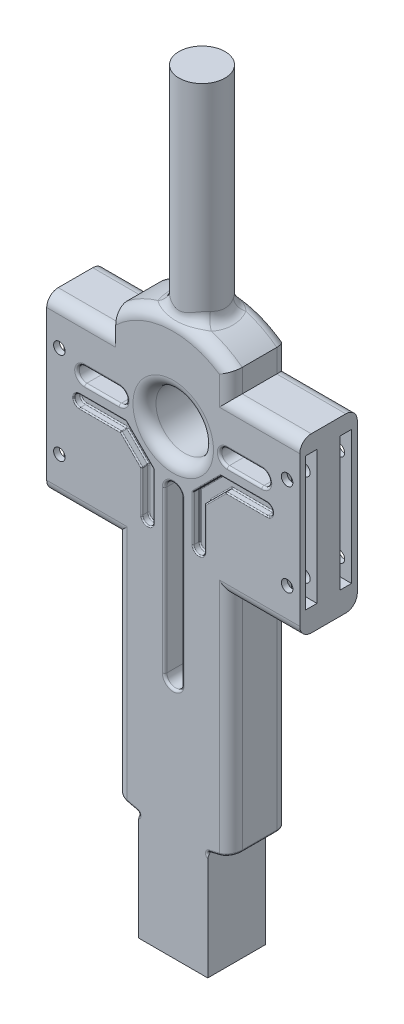
SolidWorks part; units mm, degrees
ref_plane "Спереди" through (0, 0, 0) normal (0, 0, 1) x (1, 0, 0)
ref_plane "Сверху" through (0, 0, 0) normal (0, 1, 0) x (1, 0, 0)
ref_plane "Справа" through (0, 0, 0) normal (1, 0, 0) x (0, 0, -1)
sketch "Эскиз1" plane through (0, 0, 0) normal (0, 0, 1) x (1, 0, 0)
  line L0 (-25, 0) -> (25, 0) construction
  line L5 (25, 0) -> (25, 97.3699)
  line L6 (25, 182.3699) -> (-25, 182.3699) construction
  line L7 (0, 0) -> (0, 137.8365) construction
  line L8 (-25, 0) -> (-25, 97.3699)
  line L9 (25, 172.3699) -> (55, 172.3699)
  line L10 (55, 172.3699) -> (55, 97.3699)
  line L11 (55, 97.3699) -> (25, 97.3699)
  line L12 (-55, 97.3699) -> (-25, 97.3699)
  line L13 (-55, 172.3699) -> (-55, 97.3699)
  line L14 (-25, 172.3699) -> (-55, 172.3699)
  line L15 (-25, 172.3699) -> (-25, 182.3699)
  line L16 (25, 172.3699) -> (25, 182.3699)
  arc A1 (25, 182.3699) -> (-25, 182.3699) centre (0, 150) ccw
  circle A2 centre (0, 150) radius 12.5
  arc A3 (-25, 0) -> (25, 0) centre (0, 74.94) ccw
  point P0 (0, 0)
  point P9 (0, 182.3699)
  dimension "D1" = 50
  dimension "D2" = 40.9
  dimension "D3" = 25
  dimension "D5" = 79
  dimension "D4" = 150
  dimension "D6" = 30
  dimension "D7" = 75
  dimension "D8" = 10
extrude "Бобышка-Вытянуть1" add sketch "Эскиз1" along normal blind 25
fillet "Скругление1" radius 5 2 edges at (12.5, 150, 0) (12.5, 150, 25)
fillet "Скругление2" radius 5 16 edges at (-25, 48.6849, 25) (-25, 48.6849, 0) (-40, 97.3699, 0) (-40, 97.3699, 25) (25, 48.6849, 0) (40, 97.3699, 0) (25, 48.6849, 25) (40, 97.3699, 25) (-40, 172.3699, 25) (-40, 172.3699, 0) (0, 190.9, 0) (25, 177.3699, 0) (40, 172.3699, 0) (40, 172.3699, 25) (25, 177.3699, 25) (0, 190.9, 25)
ref_plane "Плоскость1" through (0, 180, 0) normal (0, 1, 0) x (1, 0, 0)
sketch "Эскиз2" plane through (0, 180, 0) normal (0, 1, 0) x (1, 0, 0)
  line L0 (0, 0) -> (0, -25) construction
  line L1 (-25, -25) -> (20, -25) construction
  circle A0 centre (0, -12.5) radius 10
  dimension "D1" = 20
extrude "Бобышка-Вытянуть2" add sketch "Эскиз2" along normal blind 100
fillet "Скругление3" radius 5 4 edges at (-1.9459, 190.288, 2.6911) (-9.7288, 189.7261, 10.187) (9.9937, 189.6603, 12.8546) (1.9198, 190.2866, 22.314)
sketch "Эскиз3" plane through (0, 0, 0) normal (0, 0, 1) x (1, 0, 0)
  line L0 (0, 222.8155) -> (0, 47.6658) construction
  line L1 (23.5, 150) -> (38.5, 150) construction
  line L2 (78.8977, 150) -> (-76.0717, 150) construction
  line L3 (23.5, 153.3365) -> (38.5, 153.3365)
  line L4 (23.5, 146.6635) -> (38.5, 146.6635)
  line L5 (50, 180) -> (-50, 180) construction
  line L6 (37.4973, 140.3809) -> (21.8861, 140.3809) construction
  line L7 (21.8861, 140.3809) -> (7.5052, 126) construction
  line L8 (7.5052, 126) -> (7.5052, 110.5792) construction
  line L9 (37.4973, 136.3809) -> (23.5429, 136.3809) construction
  line L10 (23.5429, 136.3809) -> (11.5052, 124.3431) construction
  line L11 (11.5052, 124.3431) -> (11.5052, 110.5792) construction
  line L13 (-23.5, 150) -> (-38.5, 150) construction
  line L14 (-23.5, 153.3365) -> (-38.5, 153.3365)
  line L15 (-23.5, 146.6635) -> (-38.5, 146.6635)
  line L16 (-23.5429, 136.3809) -> (-11.5052, 124.3431) construction
  line L17 (-37.4973, 136.3809) -> (-23.5429, 136.3809) construction
  line L18 (-37.4973, 140.3809) -> (-21.8861, 140.3809) construction
  line L19 (-21.8861, 140.3809) -> (-7.5052, 126) construction
  line L20 (-7.5052, 126) -> (-7.5052, 110.5792) construction
  line L21 (-11.5052, 124.3431) -> (-11.5052, 110.5792) construction
  line L22 (0, 125) -> (0, 55) construction
  line L23 (3.75, 125) -> (3.75, 55)
  line L24 (-3.75, 125) -> (-3.75, 55)
  arc A0 (23.5, 153.3365) -> (23.5, 146.6635) centre (23.5, 150) ccw
  arc A1 (38.5, 146.6635) -> (38.5, 153.3365) centre (38.5, 150) ccw
  arc A2 (7.5052, 110.5792) -> (11.5052, 110.5792) centre (9.5052, 110.5019) ccw construction
  arc A3 (37.4973, 136.3809) -> (37.4973, 140.3809) centre (37.4973, 138.3809) ccw construction
  arc A4 (-23.5, 153.3365) -> (-23.5, 146.6635) centre (-23.5, 150) cw
  arc A5 (-38.5, 146.6635) -> (-38.5, 153.3365) centre (-38.5, 150) cw
  arc A6 (-37.4973, 136.3809) -> (-37.4973, 140.3809) centre (-37.4973, 138.3809) cw construction
  arc A7 (-7.5052, 110.5792) -> (-11.5052, 110.5792) centre (-9.5052, 110.5019) cw construction
  arc A8 (3.75, 125) -> (-3.75, 125) centre (0, 125) ccw
  arc A9 (-3.75, 55) -> (3.75, 55) centre (0, 55) ccw
  point P5 (0, 90)
  point P8 (31, 150)
  point P27 (-31, 150)
  dimension "D6" = 4.003
  dimension "D1" = 15
  dimension "D2" = 6.673
  dimension "D3" = 31
  dimension "D4" = 30
  dimension "D5" = 4
  dimension "D7" = 24
  dimension "D8" = 19.2381
  dimension "D9" = 7.5052
  dimension "D10" = 135
  dimension "D11" = 15.4981
  dimension "D12" = 15.6112
  dimension "D13" = 70
  dimension "D14" = 90
  dimension "D15" = 7.5
extrude "Вырез-Вытянуть2" cut sketch "Эскиз3" against normal through all both and the other way through all
fillet "Скругление4" radius 1 24 edges at (-41.8365, 150, 0) (-31, 153.3365, 0) (-20.1635, 150, 0) (20.1635, 150, 0) (31, 153.3365, 0) (41.8365, 150, 0) (-3.75, 90, 0) (0, 128.75, 0) (3.75, 90, 0) (0, 128.75, 25) (3.75, 90, 25) (0, 51.25, 25) (-31, 153.3365, 25) (-20.1635, 150, 25) (31, 153.3365, 25) (41.8365, 150, 25) (31, 146.6635, 25) (-31, 146.6635, 0) (-31, 146.6635, 25) (31, 146.6635, 0) (0, 51.25, 0) (-3.75, 90, 25) (-41.8365, 150, 25) (20.1635, 150, 25)
sketch "Эскиз4" plane through (0, 0, 0) normal (0, 0, 1) x (1, 0, 0)
  line L0 (0, 180) -> (0, 62.1656) construction
  line L1 (50, 180) -> (-50, 180) construction
  line L2 (8.6711, 109.7427) -> (8.6711, 129.7427)
  line L3 (8.6711, 129.7427) -> (20.6919, 141.7635)
  line L4 (20.6919, 141.7635) -> (40.6919, 141.7635)
  line L5 (4.75, 125) -> (4.75, 55) construction
  line L6 (38.5, 145.6635) -> (23.5, 145.6635) construction
  line L7 (13.6711, 109.7427) -> (13.6711, 127.6716)
  line L8 (13.6711, 127.6716) -> (22.7629, 136.7635)
  line L9 (22.7629, 136.7635) -> (40.6919, 136.7635)
  line L10 (-8.6711, 129.7427) -> (-20.6919, 141.7635)
  line L11 (-8.6711, 109.7427) -> (-8.6711, 129.7427)
  line L12 (-13.6711, 109.7427) -> (-13.6711, 127.6716)
  line L13 (-13.6711, 127.6716) -> (-22.7629, 136.7635)
  line L14 (-22.7629, 136.7635) -> (-40.6919, 136.7635)
  line L15 (-20.6919, 141.7635) -> (-40.6919, 141.7635)
  arc A0 (8.6711, 109.7427) -> (13.6711, 109.7427) centre (11.1711, 109.7427) ccw
  arc A1 (40.6919, 136.7635) -> (40.6919, 141.7635) centre (40.6919, 139.2635) ccw
  arc A2 (-8.6711, 109.7427) -> (-13.6711, 109.7427) centre (-11.1711, 109.7427) cw
  arc A3 (-40.6919, 136.7635) -> (-40.6919, 141.7635) centre (-40.6919, 139.2635) cw
  dimension "D1" = 3.9211
  dimension "D2" = 3.9
  dimension "D3" = 135
  dimension "D4" = 17
  dimension "D5" = 5
  dimension "2" = 20
  dimension "D6" = 20
extrude "Вырез-Вытянуть3" cut sketch "Эскиз4" along normal blind 3
fillet "Скругление5" radius 0.5 12 edges at (-13.6711, 118.7071, 0) (-31.7274, 136.7635, 0) (-11.1711, 107.2427, 0) (-43.1919, 139.2635, 0) (-8.6711, 119.7427, 0) (-30.6919, 141.7635, 0) (-18.217, 132.2175, 0) (-14.6815, 135.7531, 0) (-22.7629, 136.7635, 1.5) (-13.6711, 127.6716, 1.5) (-8.6711, 129.7427, 1.5) (-20.6919, 141.7635, 1.5)
fillet "Скругление6" radius 0.5 12 edges at (13.6711, 118.7071, 0) (11.1711, 107.2427, 0) (8.6711, 119.7427, 0) (14.6815, 135.7531, 0) (31.7274, 136.7635, 0) (30.6919, 141.7635, 0) (18.217, 132.2175, 0) (43.1919, 139.2635, 0) (22.7629, 136.7635, 1.5) (13.6711, 127.6716, 1.5) (8.6711, 129.7427, 1.5) (20.6919, 141.7635, 1.5)
fillet "Скругление7" radius 0.5 24 edges at (-20.7076, 141.7254, 3) (-14.6815, 135.7531, 3) (-8.7091, 129.7269, 3) (-8.6711, 119.6391, 3) (-11.1711, 107.2427, 3) (-13.6711, 118.6036, 3) (-13.7091, 127.6558, 3) (-18.217, 132.2175, 3) (-22.7787, 136.7254, 3) (-31.831, 136.7635, 3) (-43.1919, 139.2635, 3) (20.7076, 141.7254, 3) (30.7954, 141.7635, 3) (43.1919, 139.2635, 3) (31.831, 136.7635, 3) (22.7787, 136.7254, 3) (18.217, 132.2175, 3) (13.7091, 127.6558, 3) (13.6711, 118.6036, 3) (11.1711, 107.2427, 3) (8.6711, 119.6391, 3) (8.7091, 129.7269, 3) (-30.7954, 141.7635, 3) (14.6815, 135.7531, 3)
sketch "Эскиз5" plane through (0, 0, 25) normal (0, 0, 1) x (1, 0, 0)
  line L0 (0, 180) -> (0, 39.8773) construction
  line L1 (50, 180) -> (-50, 180) construction
  line L2 (8.65, 109.7427) -> (8.65, 129.7427)
  line L3 (8.65, 129.7427) -> (20.6708, 141.7635)
  line L4 (20.6708, 141.7635) -> (40.6708, 141.7635)
  line L5 (13.65, 109.7427) -> (13.65, 127.6716)
  line L6 (4.75, 125) -> (4.75, 55) construction
  line L7 (38.5, 145.6635) -> (23.5, 145.6635) construction
  line L8 (13.65, 127.6716) -> (22.7419, 136.7635)
  line L9 (22.7419, 136.7635) -> (40.6708, 136.7635)
  line L10 (-13.65, 109.7427) -> (-13.65, 127.6716)
  line L11 (-8.65, 109.7427) -> (-8.65, 129.7427)
  line L12 (-13.65, 127.6716) -> (-22.7419, 136.7635)
  line L13 (-8.65, 129.7427) -> (-20.6708, 141.7635)
  line L14 (-20.6708, 141.7635) -> (-40.6708, 141.7635)
  line L15 (-22.7419, 136.7635) -> (-40.6708, 136.7635)
  arc A0 (8.65, 109.7427) -> (13.65, 109.7427) centre (11.15, 109.7427) ccw
  arc A1 (40.6708, 136.7635) -> (40.6708, 141.7635) centre (40.6708, 139.2635) ccw
  arc A2 (-8.65, 109.7427) -> (-13.65, 109.7427) centre (-11.15, 109.7427) cw
  arc A3 (-40.6708, 136.7635) -> (-40.6708, 141.7635) centre (-40.6708, 139.2635) cw
  dimension "D1" = 20
  dimension "D2" = 17
  dimension "D3" = 20
  dimension "D4" = 135
  dimension "D5" = 3.9
  dimension "D6" = 3.9
  dimension "D7" = 5
extrude "Вырез-Вытянуть4" cut sketch "Эскиз5" against normal blind 3
fillet "Скругление8" radius 0.5 40 edges at (-13.65, 118.7071, 25) (-31.7063, 136.7635, 25) (-30.6708, 141.7635, 22) (-8.65, 119.7427, 22) (-11.15, 107.2427, 25) (-43.1708, 139.2635, 25) (-43.1708, 139.2635, 22) (-11.15, 107.2427, 22) (-8.65, 119.7427, 25) (-30.6708, 141.7635, 25) (-31.7063, 136.7635, 22) (-13.65, 118.7071, 22) (31.7063, 136.7635, 25) (43.1708, 139.2635, 25) (8.65, 119.7427, 25) (11.15, 107.2427, 25) (30.6708, 141.7635, 22) (43.1708, 139.2635, 22) (13.65, 118.7071, 22) (11.15, 107.2427, 22) (-8.65, 129.7427, 23.5) (-14.6604, 135.7531, 22) (-20.6708, 141.7635, 23.5) (-14.6604, 135.7531, 25) (22.7419, 136.7635, 23.5) (13.65, 127.6716, 23.5) (20.6708, 141.7635, 23.5) (8.65, 129.7427, 23.5) (30.6708, 141.7635, 25) (14.6604, 135.7531, 25) (13.65, 118.7071, 25) (18.1959, 132.2175, 25) (31.7063, 136.7635, 22) (18.1959, 132.2175, 22) (8.65, 119.7427, 22) (14.6604, 135.7531, 22) (-18.1959, 132.2175, 25) (-18.1959, 132.2175, 22) (-22.7419, 136.7635, 23.5) (-13.65, 127.6716, 23.5)
sketch "Эскиз6" plane through (-55, 0, 0) normal (-1, 0, 0) x (0, 0, 1)
  line L0 (12.5, 182.3699) -> (12.5, 74.6453) construction
  line L1 (20, 182.3699) -> (5, 182.3699) construction
  line L2 (0, 134.8699) -> (25, 134.8699) construction
  line L3 (0, 167.3699) -> (0, 102.3699) construction
  line L4 (25, 167.3699) -> (25, 102.3699) construction
  line L5 (2.5, 163.8699) -> (2.5, 105.8699)
  line L6 (2.5, 105.8699) -> (7.5, 105.8699)
  line L7 (7.5, 105.8699) -> (7.5, 163.8699)
  line L8 (7.5, 163.8699) -> (2.5, 163.8699)
  line L9 (22.5, 105.8699) -> (17.5, 105.8699)
  line L10 (17.5, 105.8699) -> (17.5, 163.8699)
  line L11 (17.5, 163.8699) -> (22.5, 163.8699)
  line L12 (22.5, 163.8699) -> (22.5, 105.8699)
  dimension "D1" = 29
  dimension "D2" = 29
  dimension "D3" = 5
  dimension "D4" = 10
extrude "Вырез-Вытянуть5" cut sketch "Эскиз6" against normal blind 11
sketch "Эскиз7" plane through (55, 0, 0) normal (1, 0, 0) x (0, 0, -1)
  line L0 (-12.5, 182.3699) -> (-12.5, 90.6991) construction
  line L1 (-20, 182.3699) -> (-5, 182.3699) construction
  line L2 (-25, 136.2635) -> (0, 136.2635) construction
  line L3 (-22.5, 165.2635) -> (-22.5, 107.2635)
  line L4 (-22.5, 107.2635) -> (-17.5, 107.2635)
  line L5 (-17.5, 107.2635) -> (-17.5, 165.2635)
  line L6 (-17.5, 165.2635) -> (-22.5, 165.2635)
  line L7 (-7.5, 107.2635) -> (-7.5, 165.2635)
  line L8 (-2.5, 107.2635) -> (-7.5, 107.2635)
  line L9 (-2.5, 165.2635) -> (-2.5, 107.2635)
  line L10 (-7.5, 165.2635) -> (-2.5, 165.2635)
  point P9 (-20, 107.2635)
  dimension "D1" = 29
  dimension "D2" = 29
  dimension "D3" = 5
  dimension "D4" = 10
  dimension "D5" = 2.1064
  dimension "D6" = 4.8936
extrude "Вырез-Вытянуть6" cut sketch "Эскиз7" against normal blind 11
sketch "Эскиз8" plane through (0, 0, 0) normal (0, 1, 0) x (1, 0, 0)
  line L0 (0, -43.6182) -> (0, 31.1876) construction
  line L1 (-25, -12.5) -> (25, -12.5) construction
  line L2 (-25, -20) -> (-25, -5) construction
  line L3 (25, -20) -> (25, -5) construction
  line L27 (-15, -25) -> (15, -25)
  line L28 (-15, 0) -> (15, 0)
  line L30 (-15, -25) -> (-15, 0)
  line L31 (15, -25) -> (15, 0)
  dimension "D1" = 90
  dimension "D2" = 25
  dimension "D3" = 15
  dimension "D4" = 15
  dimension "D5" = 12.5
  dimension "D6" = 25
extrude "Бобышка-Вытянуть3" add sketch "Эскиз8" against normal blind 50
fillet "Скругление10" radius 1 12 edges at (-23.9929, -0.3285, 1.9906) (-25, 0, 12.5) (-23.2161, -0.5717, 23.8284) (-17.5092, -2.0953, 25) (-15, -2.6229, 12.5) (-17.5092, -2.0953, 0) (23.9929, -0.3285, 23.0094) (25, 0, 12.5) (23.2161, -0.5717, 1.1716) (17.5092, -2.0953, 0) (15, -2.6229, 12.5) (17.5092, -2.0953, 25) tangent propagation no
sketch "Эскиз10" plane through (0, 0, 0) normal (0, 0, -1) x (-1, 0, 0)
  line L0 (-55, 134.8699) -> (59.9201, 134.8699) construction
  line L1 (-55, 102.3699) -> (-55, 167.3699) construction
  line L2 (55, 167.3699) -> (55, 102.3699) construction
  line L3 (0, 180) -> (0, 101.1491) construction
  line L4 (50, 180) -> (-50, 180) construction
  circle A0 centre (49.5, 154.8699) radius 2.5
  circle A1 centre (49.5, 114.8699) radius 2.5
  circle A2 centre (-49.5, 114.8699) radius 2.5
  circle A3 centre (-49.5, 154.8699) radius 2.5
  dimension "D1" = 5
  dimension "D2" = 5
  dimension "D3" = 40
  dimension "D4" = 20
  dimension "D5" = 5.5
  dimension "D6" = 5.5
extrude "Вырез-Вытянуть8" cut sketch "Эскиз10" against normal blind 60
sketch "Эскиз9" plane through (0, 0, 25) normal (0, 0, 1) x (1, 0, 0)
  line L0 (0, 180) -> (0, 89.4176) construction
  line L1 (50, 180) -> (-50, 180) construction
  line L2 (55, 102.3699) -> (55, 167.3699) construction
  line L3 (55, 167.3699) -> (20, 167.3699) construction
  line L4 (20, 102.3699) -> (55, 102.3699) construction
  circle A0 centre (50, 157.3699) radius 2.5
  circle A1 centre (50, 114.3699) radius 2.5
  circle A2 centre (-50, 114.3699) radius 2.5
  circle A3 centre (-50, 157.3699) radius 2.5
  dimension "D1" = 5
  dimension "D2" = 5
  dimension "D3" = 5
  dimension "D4" = 5
  dimension "D5" = 10
  dimension "D6" = 12
  dimension "D7" = 43
